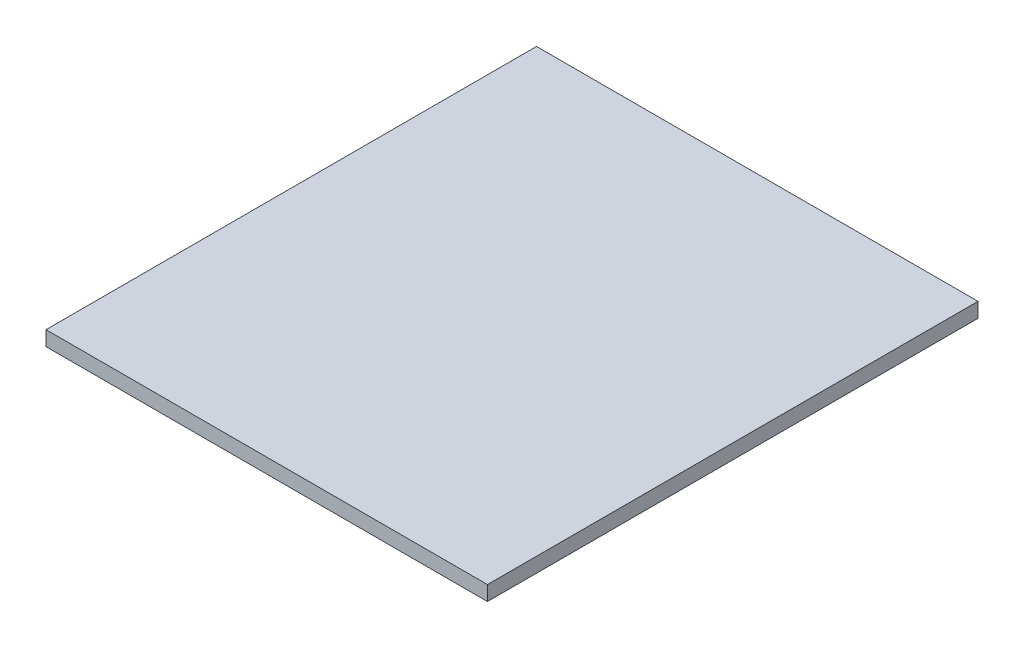
SolidWorks part; units mm, degrees
ref_plane "Front Plane" through (0, 0, 0) normal (0, 0, 1) x (1, 0, 0)
ref_plane "Top Plane" through (0, 0, 0) normal (0, 1, 0) x (1, 0, 0)
ref_plane "Right Plane" through (0, 0, 0) normal (1, 0, 0) x (0, 0, -1)
sketch "Sketch1" plane through (0, 0, 0) normal (0, 1, 0) x (1, 0, 0)
  line L1 (0, 50) -> (-90, 50)
  line L2 (0, 50) -> (0, -50)
  line L3 (0, -50) -> (-90, -50)
  line L4 (-90, 50) -> (-90, -50)
  point P4 (0, 0)
  dimension "D1" = 100
  dimension "D2" = 90
extrude "Boss-Extrude1" add sketch "Sketch1" along normal blind 3
